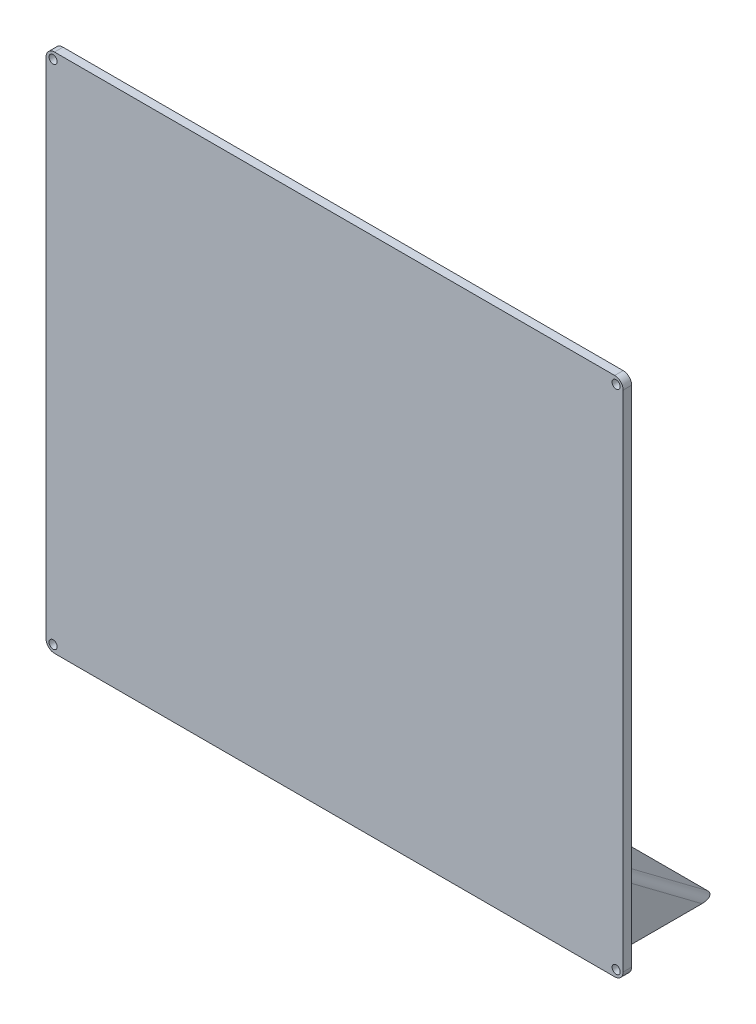
SolidWorks part; units mm, degrees
ref_plane "Plan de face" through (0, 0, 0) normal (0, 0, 1) x (1, 0, 0)
ref_plane "Plan de dessus" through (0, 0, 0) normal (0, 1, 0) x (1, 0, 0)
ref_plane "Plan de droite" through (0, 0, 0) normal (1, 0, 0) x (0, 0, -1)
sketch "Esquisse1" plane through (0, 0, 0) normal (0, 0, 1) x (1, 0, 0)
  line L1 (0, 0) -> (205, 0)
  line L2 (0, 0) -> (0, 185)
  line L3 (0, 185) -> (205, 185)
  line L4 (205, 0) -> (205, 185)
  dimension "D1" = 205
  dimension "D2" = 185
extrude "Boss.-Extru.1" add sketch "Esquisse1" along normal blind 3
sketch "Esquisse3" plane through (0, 0, 0) normal (0, 0, -1) x (-1, 0, 0)
  line L0 (-200, 180) -> (-205, 185) construction
  line L1 (-205, 185) -> (-200, 185)
  line L2 (-205, 185) -> (-205, 180)
  line L3 (-205, 180) -> (-200, 180)
  line L4 (-200, 185) -> (-200, 180)
  line L5 (-205, 180) -> (-200, 185) construction
  line L6 (-5, 180) -> (0, 185) construction
  line L7 (0, 185) -> (-5, 185)
  line L8 (0, 185) -> (0, 180)
  line L9 (0, 180) -> (-5, 180)
  line L10 (-5, 185) -> (-5, 180)
  line L11 (-5, 185) -> (0, 180) construction
  line L12 (-5, 0) -> (0, 5) construction
  line L13 (0, 0) -> (-5, 0)
  line L14 (0, 0) -> (0, 5)
  line L15 (0, 5) -> (-5, 5)
  line L16 (-5, 0) -> (-5, 5)
  line L17 (-5, 5) -> (0, 0) construction
  line L18 (-200, 5) -> (-205, 0) construction
  line L19 (-205, 0) -> (-200, 0)
  line L20 (-205, 0) -> (-205, 5)
  line L21 (-205, 5) -> (-200, 5)
  line L22 (-200, 0) -> (-200, 5)
  line L23 (-205, 5) -> (-200, 0) construction
  point P23 (-202.5, 2.5)
  point P25 (-2.5, 2.5)
  point P27 (-2.5, 182.5)
  point P29 (-202.5, 182.5)
  dimension "D1" = 5
  dimension "D2" = 5
  dimension "D3" = 5
  dimension "D4" = 5
  dimension "D5" = 5
  dimension "D6" = 5
  dimension "D7" = 5
  dimension "D8" = 5
hole_wizard "Dégagement M2.51" positions "Esquisse3" profile "Esquisse5" hole size "M2.5" standard "Ansi Metric" end condition through all
sketch "Esquisse5" plane through (202.5, 182.5, 0) normal (1, 0, 0) x (0, 1, 0)
  line L0 (0, 0) -> (0, 3)
  line L1 (0, 3) -> (1.45, 3)
  line L2 (1.45, 3) -> (1.45, 0)
  line L5 (1.45, 0) -> (0, 0)
  line L11 (0, -6.35) -> (0, 107.95) construction
  dimension "Diamètre du perçage jusqu'au prochain" = 2.9
  dimension "Profondeur du perçage jusqu'au prochain" = 3
fillet "Congé1" radius 3 1 edges at (205, 0, 1.5)
fillet "Congé2" radius 3 3 edges at (0, 0, 1.5) (0, 185, 1.5) (205, 185, 1.5)
sketch "Esquisse6" plane through (0, 0, 0) normal (1, 0, 0) x (0, 0, -1)
  line L0 (0, 0) -> (40, 0)
  line L1 (0, 0) -> (0, 30)
  line L2 (0, 3) -> (0, 182) construction
  line L3 (0, 30) -> (40, 0)
  dimension "D1" = 30
  dimension "D2" = 40
extrude "Boss.-Extru.3" add sketch "Esquisse6" along normal blind 195
extrude "Enlèv. mat.-Extru.2" cut sketch "Esquisse6<3>" along normal blind 155
sketch "Esquisse6<3>" plane through (0, 0, 0) normal (1, 0, 0) x (0, 0, -1) same geometry as "Esquisse6"
extrude "Boss.-Extru.4" add sketch "Esquisse6<4>" along normal blind 50
sketch "Esquisse6<4>" plane through (0, 0, 0) normal (1, 0, 0) x (0, 0, -1) same geometry as "Esquisse6"
extrude "Enlèv. mat.-Extru.3" cut sketch "Esquisse6<5>" along normal blind 10
sketch "Esquisse6<5>" plane through (0, 0, 0) normal (1, 0, 0) x (0, 0, -1) same geometry as "Esquisse6"
fillet "Congé3" radius 3 10 edges at (10, 15, 0) (155, 15, 0) (195, 15, 0) (50, 15, -20) (50, 15, 0) (10, 15, -20) (30, 30, 0) (155, 15, -20) (195, 15, -20) (175, 30, 0)
